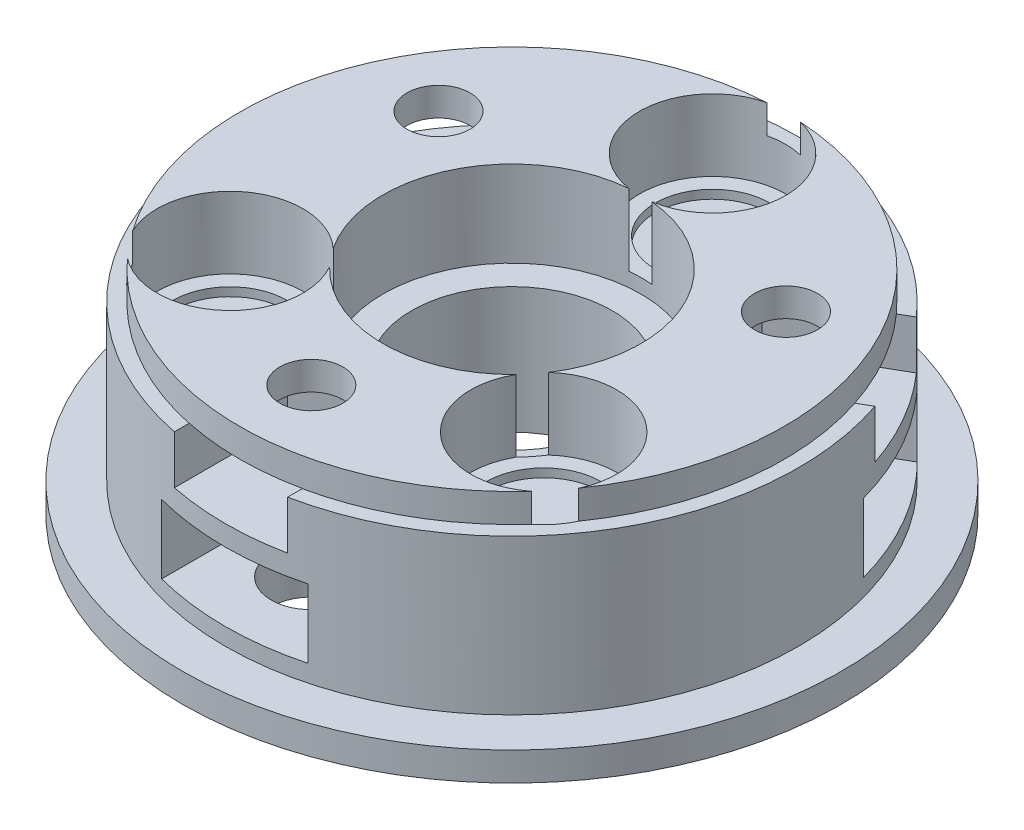
SolidWorks part; units mm, degrees
ref_plane "Front Plane" through (0, 0, 0) normal (0, 0, 1) x (1, 0, 0)
ref_plane "Top Plane" through (0, 0, 0) normal (0, 1, 0) x (1, 0, 0)
ref_plane "Right Plane" through (0, 0, 0) normal (1, 0, 0) x (0, 0, -1)
sketch "Sketch2" plane through (0, 0, 0) normal (0, 1, 0) x (1, 0, 0)
  circle A0 centre (0, 0) radius 11.5
  dimension "D1" = 23
extrude "Boss-Extrude1" add sketch "Sketch2" along normal blind 1
sketch "Sketch3" plane through (0, 1, 0) normal (0, 1, 0) x (1, 0, 0)
  circle A0 centre (0, 0) radius 10
  dimension "D1" = 20
extrude "Boss-Extrude2" add sketch "Sketch3" along normal blind 4
ref_plane "Plane1" through (0, 4.9, 0) normal (0, -1, 0) x (-1, 0, 0)
sketch "Sketch4" plane through (0, 4.9, 0) normal (0, -1, 0) x (-1, 0, 0)
  circle A0 centre (0, 0) radius 7 construction
  circle A1 centre (0, 7) radius 2.55
  dimension "D1" = 14
  dimension "D2" = 5.1
extrude "Cut-Extrude1" cut sketch "Sketch4" against normal through all
sketch "Sketch5" plane through (0, 4.9, 0) normal (0, 1, 0) x (1, 0, 0)
  circle A0 centre (0, 7) radius 2
  dimension "D1" = 4
extrude "Cut-Extrude2" cut sketch "Sketch5" against normal blind 0.3
ref_axis "Axis1" through (0, 5, 0) along (0, -1, 0)
pattern_circular "CirPattern1" count 14 over 360 about axis through (0, 5, 0) along (0, -1, 0) skipping 1, 2, 3, 4, 6, 7, 8, 10, 11, 12, 13 of "Cut-Extrude1", "Cut-Extrude2"
sketch "Sketch7" plane through (0, 4.9, 0) normal (0, 1, 0) x (1, 0, 0)
  circle A0 centre (5.4728, -4.3644) radius 2.55 construction
  circle A1 centre (0, 0) radius 10
  circle A3 centre (-5.4728, -4.3644) radius 2.55 construction
  circle A4 centre (0, 7) radius 2.55 construction
  circle A5 centre (5.4728, -4.3644) radius 2.55
  circle A6 centre (-5.4728, -4.3644) radius 2.55
  circle A7 centre (0, 7) radius 2.55
  circle A9 centre (0, 0) radius 10
  dimension "D1" = 0
extrude "Boss-Extrude4" add sketch "Sketch7" along normal blind 1.5
sketch "Sketch6" plane through (0, 6.4, 0) normal (0, 1, 0) x (1, 0, 0)
  circle A0 centre (0, 0) radius 4.5 construction
  arc A1 (-0.5851, 9.482) -> (-0.4025, 4.482) centre (0, 7) ccw
  circle A2 centre (0, 0) radius 9.5 construction
  arc A3 (-3.7551, -2.4798) -> (-7.7781, -5.4545) centre (-5.4728, -4.3644) ccw
  arc A4 (3.2532, -3.1091) -> (7.0485, -6.3694) centre (5.4728, -4.3644) ccw
  arc A5 (0.4025, 4.482) -> (0.5851, 9.482) centre (0, 7) ccw
  arc A6 (-7.0485, -6.3694) -> (-3.2532, -3.1091) centre (-5.4728, -4.3644) ccw
  arc A7 (7.7781, -5.4545) -> (3.7551, -2.4798) centre (5.4728, -4.3644) ccw
  arc A8 (-3.7551, -2.4798) -> (-0.4025, 4.482) centre (0, 0) cw
  arc A9 (-7.7781, -5.4545) -> (-0.5851, 9.482) centre (0, 0) cw
  arc A12 (-3.2532, -3.1091) -> (3.2532, -3.1091) centre (0, 0) ccw
  arc A13 (-7.0485, -6.3694) -> (7.0485, -6.3694) centre (0, 0) ccw
  arc A14 (0.4025, 4.482) -> (3.7551, -2.4798) centre (0, 0) cw
  arc A15 (0.5851, 9.482) -> (7.7781, -5.4545) centre (0, 0) cw
  dimension "D1" = 9
  dimension "D2" = 5.1
  dimension "D3" = 19
extrude "Boss-Extrude3" add sketch "Sketch6" along normal up to surface (0.998 mm away)
sketch "Sketch8" plane through (0, 7.398, 0) normal (0, 1, 0) x (1, 0, 0)
  circle A0 centre (0, -7) radius 1.1 construction
  circle A1 centre (0, -7) radius 1.1
extrude "Cut-Extrude3" cut sketch "Sketch8" against normal offset from surface (2.69 mm away) 12.2
sketch "Sketch9" plane through (0, 4.708, 0) normal (0, 1, 0) x (1, 0, 0)
  line L0 (-1.975, -8.1403) -> (-1.975, -11.3291)
  line L1 (0, -9.2805) -> (1.975, -8.1403) construction
  line L2 (1.975, -8.1403) -> (1.975, -5.8597)
  line L3 (1.975, -5.8597) -> (0, -4.7195)
  line L4 (0, -4.7195) -> (-1.975, -5.8597)
  line L5 (-1.975, -5.8597) -> (-1.975, -8.1403)
  line L6 (-1.975, -8.1403) -> (0, -9.2805) construction
  line L7 (-1.975, -11.3291) -> (1.975, -11.3291)
  line L8 (1.975, -11.3291) -> (1.975, -8.1403)
  circle A0 centre (0, -7) radius 1.975 construction
  circle A1 centre (0, 0) radius 11.5 construction
  dimension "D1" = 3.95
extrude "Cut-Extrude4" cut sketch "Sketch9" along normal blind 1.7 contours L7 L8 L2 L3 L4 L5 L0
pattern_circular "CirPattern2" count 3 over 360 about axis through (0, 5, 0) along (0, -1, 0) of "Cut-Extrude4", "Cut-Extrude3"
sketch "Sketch10" plane through (0, 0, 0) normal (0, -1, 0) x (1, 0, 0)
  circle A0 centre (0, 0) radius 8 construction
  circle A1 centre (0, 8) radius 1.35
  dimension "D1" = 16
  dimension "D2" = 2.7
sketch "Sketch11" [suppressed] plane through (0, 0, 0) normal (0, -1, 0) x (1, 0, 0)
  circle A1 centre (0, 0) radius 11.5
  circle A2 centre (0, 0) radius 11.5
  dimension "D1" = 0
extrude "Boss-Extrude5" [suppressed] add sketch "Sketch11" along normal blind 3
sketch "Sketch12" [suppressed] plane through (0, -3, 0) normal (0, -1, 0) x (1, 0, 0)
  circle A0 centre (0, 8) radius 1.65
  dimension "D1" = 3.3
extrude "Cut-Extrude5" [suppressed] cut sketch "Sketch12" against normal up to surface (4 mm away) up to face at (0, 1, 10)
sketch "Sketch13" [suppressed] plane through (0, 1, 0) normal (0, 1, 0) x (1, 0, 0)
  line L0 (-2.75, -9.5877) -> (-2.75, -11.5)
  line L1 (0, -11.1754) -> (2.75, -9.5877) construction
  line L2 (2.75, -9.5877) -> (2.75, -6.4123)
  line L3 (2.75, -6.4123) -> (0, -4.8246)
  line L4 (0, -4.8246) -> (-2.75, -6.4123)
  line L5 (-2.75, -6.4123) -> (-2.75, -9.5877)
  line L6 (-2.75, -9.5877) -> (0, -11.1754) construction
  line L7 (-2.75, -11.5) -> (2.75, -11.5)
  line L8 (2.75, -11.5) -> (2.75, -9.5877)
  circle A0 centre (0, -8) radius 2.75 construction
  circle A1 centre (0, 0) radius 11.5 construction
  dimension "D1" = 5.5
extrude "Cut-Extrude6" [suppressed] cut sketch "Sketch13" against normal blind 2.8
pattern_circular "CirPattern3" [suppressed] count 4 over 360 about axis through (0, 5, 0) along (0, -1, 0) of bodies 114
sketch "Sketch14" plane through (0, 0, 0) normal (0, -1, 0) x (1, 0, 0)
  circle A0 centre (0, 0) radius 7 construction
  circle A1 centre (0, 7) radius 1.4
  dimension "14" = 14
  dimension "D2" = 2.8
extrude "Cut-Extrude7" cut sketch "Sketch14" against normal blind 4
sketch "Sketch15" plane through (0, 4, 0) normal (0, -1, 0) x (1, 0, 0)
  line L1 (0, 4.0555) -> (2.55, 5.5278)
  line L2 (2.55, 5.5278) -> (2.55, 8.4722)
  line L3 (2.55, 8.4722) -> (0, 9.9445) construction
  line L4 (0, 9.9445) -> (-2.55, 8.4722) construction
  line L5 (-2.55, 8.4722) -> (-2.55, 5.5278)
  line L6 (-2.55, 5.5278) -> (0, 4.0555)
  line L9 (2.55, 11.5) -> (-2.55, 11.5)
  line L10 (-2.55, 8.4722) -> (-2.55, 11.5)
  line L11 (2.55, 8.4722) -> (2.55, 11.5)
  circle A0 centre (0, 7) radius 2.55 construction
  circle A2 centre (0, 0) radius 11.5 construction
  dimension "D1" = 5.1
extrude "Cut-Extrude8" cut sketch "Sketch15" along normal blind 2.4
pattern_circular "CirPattern4" count 3 over 360 about axis through (0, 5, 0) along (0, -1, 0) of "Cut-Extrude7", "Cut-Extrude8"
sketch "Sketch16" plane through (0, 6.4, 0) normal (0, 1, 0) x (1, 0, 0)
  circle A0 centre (0, 0) radius 4.5
  arc A1 (3.7551, -2.4798) -> (0.4025, 4.482) centre (0, 0) ccw construction
extrude "Cut-Extrude9" cut sketch "Sketch16" against normal blind 2
sketch "Sketch17" plane through (0, 4.4, 0) normal (0, 1, 0) x (1, 0, 0)
  circle A0 centre (0, 0) radius 3.5
  dimension "D1" = 7
extrude "Cut-Extrude10" cut sketch "Sketch17" against normal through all
